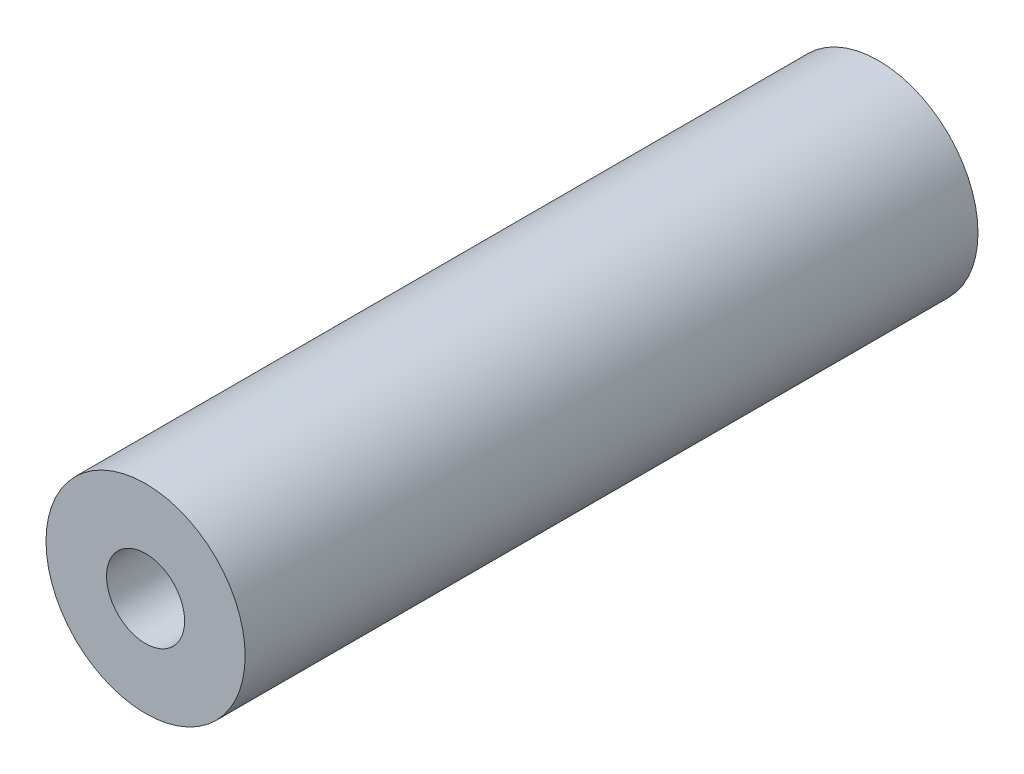
SolidWorks part; units mm, degrees
ref_plane "Front Plane" through (0, 0, 0) normal (0, 0, 1) x (1, 0, 0)
ref_plane "Top Plane" through (0, 0, 0) normal (0, 1, 0) x (1, 0, 0)
ref_plane "Right Plane" through (0, 0, 0) normal (1, 0, 0) x (0, 0, -1)
sketch "Sketch1" plane through (0, 0, 0) normal (0, 0, 1) x (1, 0, 0)
  circle A0 centre (0, 0) radius 6.35
  circle A1 centre (0, 0) radius 2.4892
  dimension "D1" = 12.7
  dimension "D2" = 4.9784
extrude "Boss-Extrude1" add sketch "Sketch1" along normal mid plane 46.736
